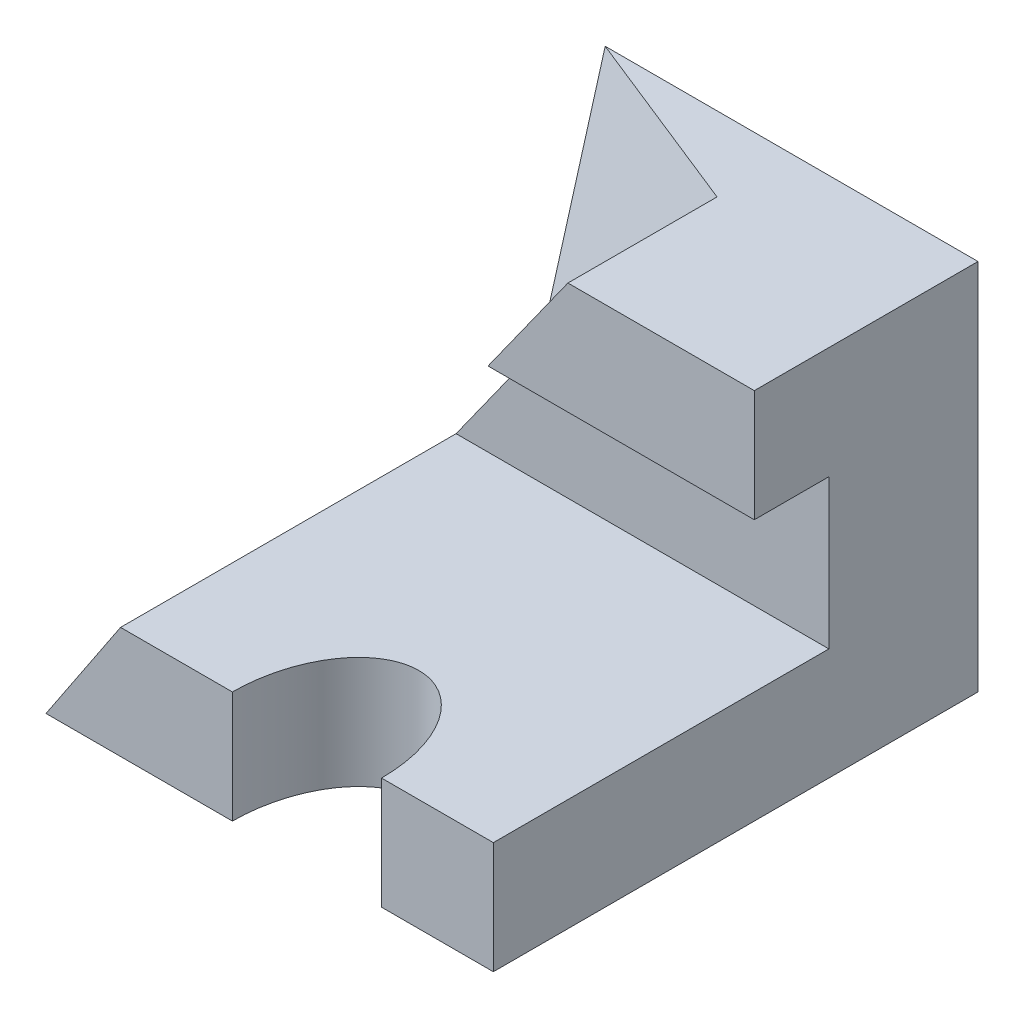
SolidWorks part; units mm, degrees
ref_plane "Front Plane" through (0, 0, 0) normal (0, 0, 1) x (1, 0, 0)
ref_plane "Top Plane" through (0, 0, 0) normal (0, 1, 0) x (1, 0, 0)
ref_plane "Right Plane" through (0, 0, 0) normal (1, 0, 0) x (0, 0, -1)
sketch "Sketch1" plane through (0, 0, 0) normal (0, 0, 1) x (1, 0, 0)
  line L0 (0, 0) -> (-35039.6653, 0) construction
  line L1 (0, 0) -> (0, -35039.6653) construction
  line L2 (0, 0) -> (50, 0)
  line L3 (50, 0) -> (50, -15)
  line L4 (50, -15) -> (-10, -15)
  line L5 (-10, -15) -> (0, 0)
  line L6 (50, 0) -> (50, 35)
  line L7 (50, 35) -> (25, 35)
  line L8 (25, 35) -> (0, 0)
  line L9 (50, 20) -> (14.2857, 20)
  line L10 (0, 0) -> (0, 35)
  line L11 (0, 35) -> (25, 35)
  dimension "D1" = 50
  dimension "D2" = 15
  dimension "D3" = 60
  dimension "D4" = 35
  dimension "D5" = 15
  dimension "D6" = 25
extrude "Boss-Extrude1" add sketch "Sketch1" along normal blind 65 contours L5 L4 L3 L2 region at (22.4242, -7.7273, 0)
extrude "Boss-Extrude2" add sketch "Sketch1<3>" along normal blind 30 separate body contours L9 L6 L7 L8 region at (34.6639, 27.0588, 0)
sketch "Sketch1<3>" plane through (0, 0, 0) normal (0, 0, 1) x (1, 0, 0) same geometry as "Sketch1"
extrude "Boss-Extrude3" add sketch "Sketch1<4>" along normal blind 20 contours L6 L9 L8 L2 region at (28.373, 9.4444, 0)
sketch "Sketch1<4>" plane through (0, 0, 0) normal (0, 0, 1) x (1, 0, 0) same geometry as "Sketch1"
extrude "Boss-Extrude4" add sketch "Sketch1<5>" along normal blind 10 contours L11 L10 L8 region at (8.3333, 23.3333, 0)
sketch "Sketch1<5>" plane through (0, 0, 0) normal (0, 0, 1) x (1, 0, 0) same geometry as "Sketch1"
ref_plane "Plane1" through (-3.2216, 2.3011, 8.0539) normal (-0.359, 0.2564, 0.8974) x (0.9333, 0.0986, 0.3452)
sketch "Sketch2" plane through (-3.2216, 2.3011, 8.0539) normal (-0.359, 0.2564, 0.8974) x (0.9333, 0.0986, 0.3452)
  line L0 (30.2369, 30.9061) -> (3.4516, 33.6533)
  line L1 (3.4516, 33.6533) -> (3.4516, -2.7472)
  line L2 (3.4516, -2.7472) -> (30.2369, 30.9061)
extrude "Cut-Extrude1" cut sketch "Sketch2" along direction (0, 0, -1) on the side of the normal blind 10
sketch "Sketch4" plane through (0, 0, 0) normal (0, 1, 0) x (1, 0, 0)
  line L0 (50, -65) -> (50, -20) construction
  line L1 (0, -65) -> (50, -65) construction
  line L2 (15, -65) -> (35, -65)
  ellipse E0 centre (25, -65) end of major axis (25, -80) minor radius 10 (35, -65) -> (15, -65) ccw
  dimension "D1" = 15
  dimension "D2" = 20
  dimension "D3" = 25
extrude "Cut-Extrude3" cut sketch "Sketch4" against normal through all
